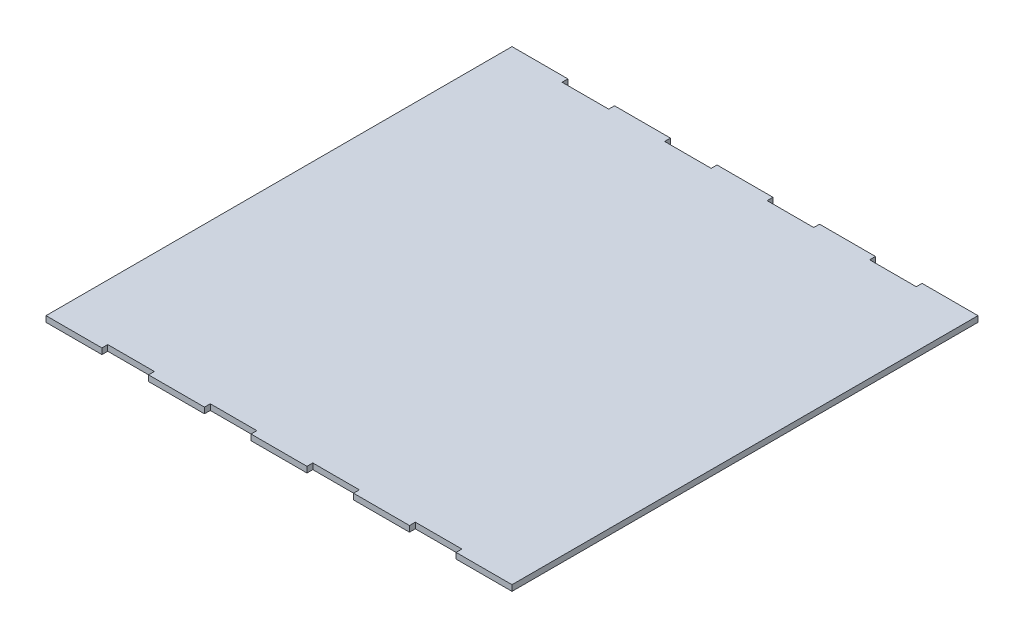
SolidWorks part; units mm, degrees
ref_plane "Front" through (0, 0, 0) normal (0, 0, 1) x (1, 0, 0)
ref_plane "Top" through (0, 0, 0) normal (0, 1, 0) x (1, 0, 0)
ref_plane "Right" through (0, 0, 0) normal (1, 0, 0) x (0, 0, -1)
sketch "Skizze1" plane through (0, 0, 0) normal (0, 1, 0) x (1, 0, 0)
  line L1 (200, 200) -> (-200, 200)
  line L2 (200, 200) -> (200, -200)
  line L3 (200, -200) -> (-200, -200)
  line L4 (-200, 200) -> (-200, -200)
  line L5 (200, 200) -> (-200, -200) construction
  line L6 (200, -200) -> (-200, 200) construction
  point P0 (0, 0)
  dimension "D1" = 400
  dimension "D2" = 400
extrude "Grundplatte" add sketch "Skizze1" along normal blind 5
ref_plane "Ebene1" through (0, 0, 0) normal (0, 0, 1) x (1, 0, 0)
ref_plane "Ebene2" through (0, 0, 0) normal (-1, 0, 0) x (0, 0, 1)
sketch "Skizze2" plane through (0, 5, 0) normal (0, 1, 0) x (1, 0, 0)
  line L0 (-200, 200) -> (-200, -200) construction
  line L5 (0, 200) -> (0, 0) construction
  line L6 (200, 200) -> (-200, 200) construction
  line L7 (152, 195) -> (200, 195) construction
  line L8 (24, 195) -> (-24, 195) construction
  line L13 (-152, 200) -> (-112, 200)
  line L14 (-152, 200) -> (-152, 195)
  line L15 (-152, 195) -> (-112, 195)
  line L16 (-112, 200) -> (-112, 195)
  line L17 (-64, 200) -> (-24, 200)
  line L18 (-64, 200) -> (-64, 195)
  line L19 (-64, 195) -> (-24, 195)
  line L20 (-24, 200) -> (-24, 195)
  line L21 (-64, 195) -> (-112, 195) construction
  line L22 (-152, 195) -> (-200, 195) construction
  line L23 (64, 195) -> (112, 195) construction
  line L24 (24, 200) -> (24, 195)
  line L25 (64, 195) -> (24, 195)
  line L42 (64, 200) -> (64, 195)
  line L43 (64, 200) -> (24, 200)
  line L44 (112, 200) -> (112, 195)
  line L45 (152, 195) -> (112, 195)
  line L46 (152, 200) -> (152, 195)
  line L63 (152, 200) -> (112, 200)
  point P12 (0, 195)
  dimension "D1" = 40
  dimension "D2" = 5
  dimension "D3" = 48
extrude "Schnitt-Linear austragen1" cut sketch "Skizze2" against normal through all
mirror "Spiegeln1" about plane through (0, 0, 0) normal (0, 0, 1) of "Schnitt-Linear austragen1"
ref_axis "Achse1" through (0, 10.2665, 0) along (0, -1, 0)
pattern_circular "Kreismuster1" [suppressed] count 2 over 90 about axis through (0, 10.2665, 0) along (0, -1, 0) of bodies 103
